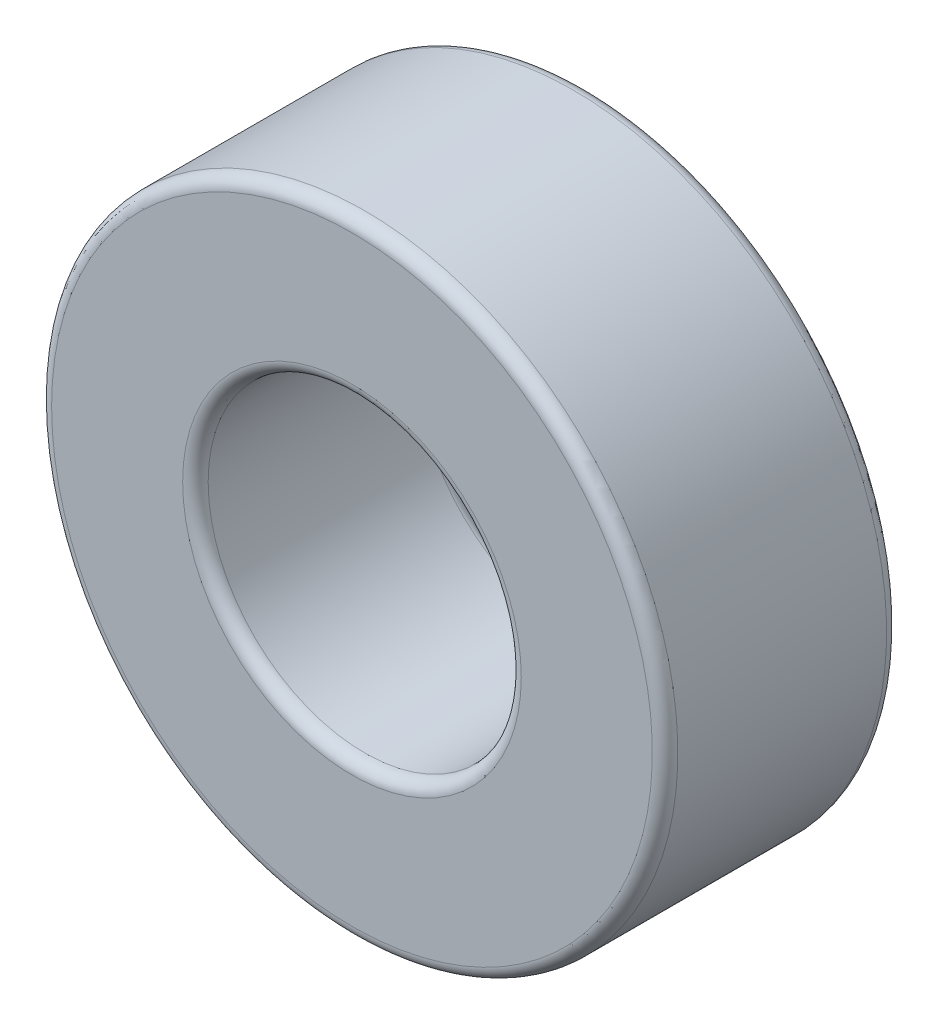
SolidWorks part; units mm, degrees
ref_plane "Front Plane" through (0, 0, 0) normal (0, 0, 1) x (1, 0, 0)
ref_plane "Top Plane" through (0, 0, 0) normal (0, 1, 0) x (1, 0, 0)
ref_plane "Right Plane" through (0, 0, 0) normal (1, 0, 0) x (0, 0, -1)
sketch "Sketch1" plane through (0, 0, 0) normal (0, 1, 0) x (1, 0, 0)
  line L0 (0, 0) -> (0, 2)
  line L1 (0.1222, 2.1222) -> (1.3778, 2.1222)
  line L2 (0.1222, -0.1222) -> (1.3778, -0.1222)
  line L3 (1.5, 2) -> (1.5, 0)
  line L4 (-1.5, 2) -> (-1.5, 0) construction
  arc A0 (0, 2) -> (0.1222, 2.1222) centre (0.1222, 2) cw
  arc A1 (0, 0) -> (0.1222, -0.1222) centre (0.1222, 0) ccw
  arc A2 (1.3778, 2.1222) -> (1.5, 2) centre (1.3778, 2) cw
  arc A3 (1.3778, -0.1222) -> (1.5, 0) centre (1.3778, 0) ccw
  dimension "D1" = 0.1222
  dimension "D3" = 0.1222
  dimension "D4" = 0.1222
  dimension "D7" = 0.1222
  dimension "D2" = 2
  dimension "D5" = 1.2556
  dimension "D6" = 1.2556
  dimension "D8" = 2
  dimension "D9" = 1.5
revolve "Revolve1" add sketch "Sketch1" angle 360 about L4
ref_axis "Axis1" through (-1.5, 0, 0) along (0, 0, -1)
